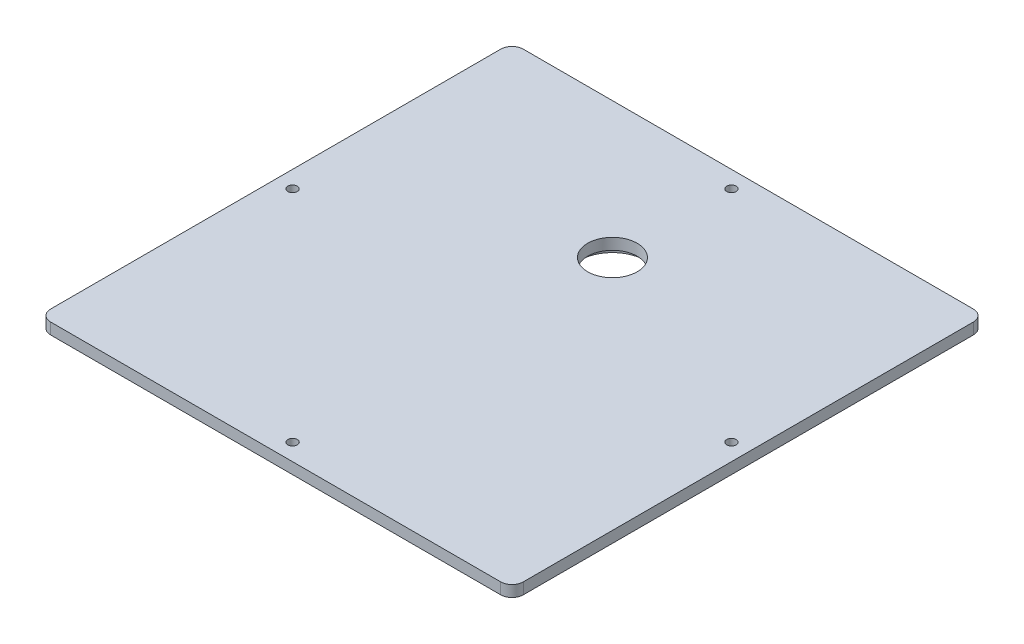
SolidWorks part; units mm, degrees
ref_plane "Front Plane" through (0, 0, 0) normal (0, 0, 1) x (1, 0, 0)
ref_plane "Top Plane" through (0, 0, 0) normal (0, 1, 0) x (1, 0, 0)
ref_plane "Right Plane" through (0, 0, 0) normal (1, 0, 0) x (0, 0, -1)
sketch "Sketch2" plane through (0, 0, 0) normal (0, 1, 0) x (1, 0, 0)
  line L1 (-105, -105) -> (105, -105)
  line L2 (-105, -105) -> (-105, 105)
  line L3 (-105, 105) -> (105, 105)
  line L4 (105, -105) -> (105, 105)
  line L5 (-105, -105) -> (105, 105) construction
  line L6 (-105, 105) -> (105, -105) construction
  point P0 (0, 0)
  dimension "D1" = 210
  dimension "D2" = 210
extrude "Boss-Extrude1" add sketch "Sketch2" along normal blind 5
sketch "Sketch3" plane through (0, 0, 0) normal (0, -1, 0) x (1, 0, 0)
  line L1 (-89.75, -89.75) -> (89.75, -89.75)
  line L2 (-89.75, -89.75) -> (-89.75, 89.75)
  line L3 (-89.75, 89.75) -> (89.75, 89.75)
  line L4 (89.75, -89.75) -> (89.75, 89.75)
  line L5 (-89.75, -89.75) -> (89.75, 89.75) construction
  line L6 (-89.75, 89.75) -> (89.75, -89.75) construction
  point P0 (0, 0)
  dimension "D1" = 179.5
  dimension "D2" = 179.5
extrude "Boss-Extrude2" add sketch "Sketch3" along normal blind 3.5 draft 2
sketch "Sketch4" plane through (0, 5, 0) normal (0, 1, 0) x (1, 0, 0)
  line L0 (-89.6278, 89.6278) -> (89.6278, 89.6278) construction
  circle A0 centre (0, 44.6278) radius 14.7
  circle A1 centre (0, 44.6278) radius 11
  dimension "D1" = 29.4
  dimension "D2" = 45
  dimension "D3" = 22
extrude "Cut-Extrude1" cut sketch "Sketch4" along normal up to surface (-5 mm away) from surface up to face at (0, 0, 0) starting at face at (0, -3.5, 0)
sketch "Sketch6" plane through (0, 5, 0) normal (0, 1, 0) x (1, 0, 0)
  line L0 (105, 105) -> (-105, 105) construction
  line L1 (-1000, 0) -> (49000, 0) construction
  line L2 (0, -1000) -> (0, 49000) construction
  line L3 (-105, 105) -> (-105, -105) construction
  circle A0 centre (0, 97.5) radius 2.1
  circle A1 centre (0, 97.5) radius 2.1
  circle A2 centre (0, 97.5) radius 2.1
  circle A3 centre (0, 97.5) radius 2.1
  circle A4 centre (0, -97.5) radius 2.1
  circle A5 centre (-97.5, 0) radius 2.1
  circle A6 centre (97.5, 0) radius 2.1
  dimension "D1" = 4.2
  dimension "D4" = 4.2
  dimension "D2" = 7.5
  dimension "D3" = 4
  dimension "D5" = 7.5
extrude "Cut-Extrude2" cut sketch "Sketch6" against normal up to surface (5 mm away) contours A2 | A5 | A4 | A6 region at (0, 5, -97.5) region at (0, 5, 97.5) region at (-97.5, 5, 0) region at (97.5, 5, 0) up to face at (0, 0, 0)
fillet "Fillet1" radius 5 4 edges at (89.6889, -1.75, 89.6889) (89.6889, -1.75, -89.6889) (-89.6889, -1.75, -89.6889) (-89.6889, -1.75, 89.6889)
extrude "Cut-Extrude3" cut sketch "Sketch4<2>" against normal up to surface (8.5 mm away) contours A1 region at (0, 5, -44.6278) up to face at (0, -3.5, -33.6278)
sketch "Sketch4<2>" plane through (0, 5, 0) normal (0, 1, 0) x (1, 0, 0) same geometry as "Sketch4"
fillet "Fillet2" radius 5 4 edges at (-105, 2.5, 105) (105, 2.5, 105) (105, 2.5, -105) (-105, 2.5, -105)
